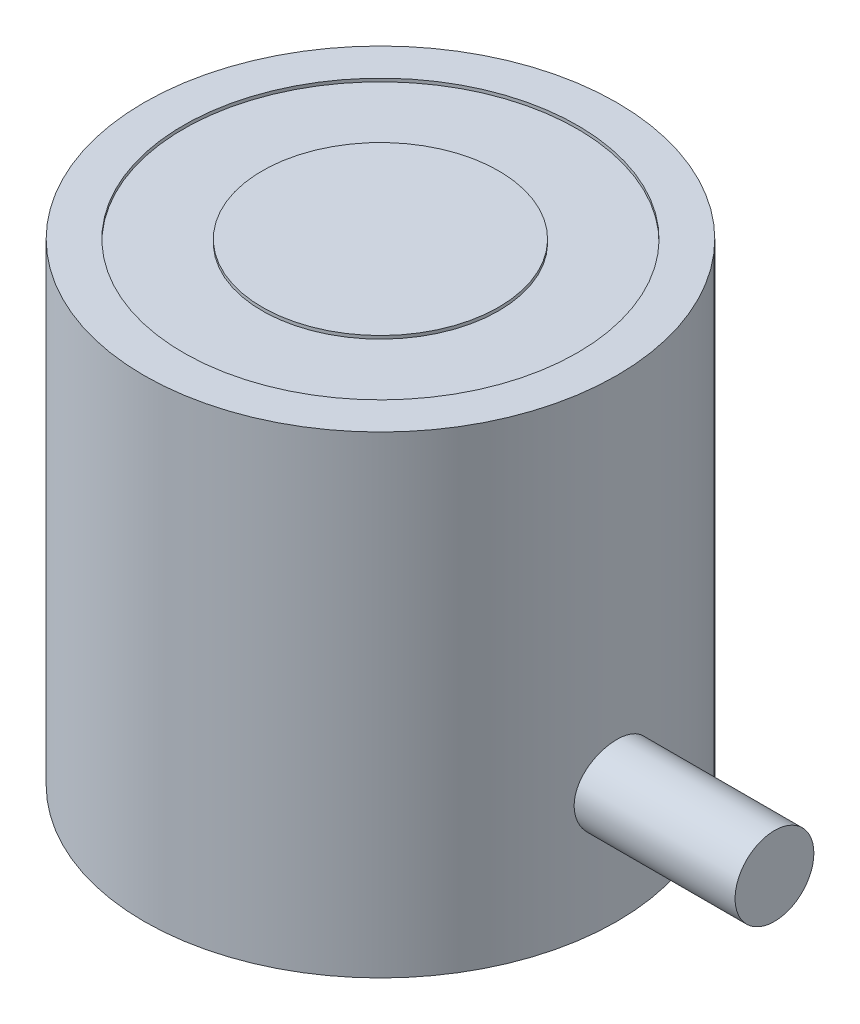
SolidWorks part; units mm, degrees
ref_plane "Front Plane" through (0, 0, 0) normal (0, 0, 1) x (1, 0, 0)
ref_plane "Top Plane" through (0, 0, 0) normal (0, 1, 0) x (1, 0, 0)
ref_plane "Right Plane" through (0, 0, 0) normal (1, 0, 0) x (0, 0, -1)
sketch "Sketch1" plane through (0, 0, 0) normal (0, 1, 0) x (1, 0, 0)
  circle A0 centre (0, 0) radius 19.05
  dimension "A" = 38.1
extrude "Boss-Extrude1" add sketch "Sketch1" along normal blind 38.1
sketch "Sketch2" plane through (0, 0, 0) normal (0, 0, 1) x (1, 0, 0)
  line L0 (-15.875, 38.1) -> (-15.875, 37.846)
  line L1 (-15.875, 37.846) -> (-9.525, 37.846)
  line L2 (-9.525, 37.846) -> (-9.525, 38.1)
  line L3 (19.05, 38.1) -> (-19.05, 38.1) construction
  line L4 (-9.525, 38.1) -> (-15.875, 38.1)
  line L5 (0, 0) -> (0, 38.1) construction
  line L6 (-19.05, 38.1) -> (-19.05, 0) construction
  dimension "D1" = 3.175
  dimension "D2" = 6.35
  dimension "D3" = 0.254
revolve "Cut-Revolve1" cut sketch "Sketch2" angle 360 about L5
sketch "Sketch3" plane through (0, 0, 0) normal (0, -1, 0) x (1, 0, 0)
  circle A0 centre (0, 0) radius 3.175
  point P3 (-3.175, 0)
  point P4 (3.175, 0)
  point P5 (0, 0)
  dimension "Hole Dia." = 6.35
extrude "Cut-Extrude1" cut sketch "Sketch3" against normal blind 12.7
sketch "Sketch4" plane through (0, 0, 0) normal (0, -1, 0) x (1, 0, 0)
  circle A1 centre (0, 0) radius 3.175
  circle A2 centre (0, 0) radius 3.175
  point P0 (-3.175, 0)
  dimension "D1" = 0
curve "Helix/Spiral1" pitch 1.27 height 13.97 turns 11 parameters "Pitch"=1.27
sketch "Sketch5" plane through (0, 0, 0) normal (0, 0, 1) x (1, 0, 0)
  line L0 (-3.3125, 0.0794) -> (-3.3125, -1.1906) construction
  line L1 (-3.3125, -1.1906) -> (-2.2126, -0.5556) construction
  line L2 (-2.2126, -0.5556) -> (-3.3125, 0.0794) construction
  line L3 (-3.175, 0) -> (-3.175, -1.1112) construction
  line L4 (-2.3501, -0.4762) -> (-2.3501, -0.635) construction
  line L5 (-2.2126, -0.5556) -> (-2.3501, -0.5556) construction
  line L6 (-2.3501, -0.5556) -> (-2.4876, -0.5556) construction
  line L7 (-3.175, -0.5556) -> (-3.3125, -0.5556) construction
  line L8 (-3.2437, -1.1509) -> (-3.2437, 0.0397)
  line L9 (-3.2437, 0.0397) -> (-2.4876, -0.3969)
  line L10 (-2.4876, -0.3969) -> (-2.4876, -0.7144)
  line L11 (-2.4876, -0.7144) -> (-3.2437, -1.1509)
  point P16 (-3.2437, -0.5556)
  dimension "D1" = 1.27
  dimension "D2" = 0.1588
sketch "Sketch6" plane through (0, 0, 0) normal (0, -1, 0) x (1, 0, 0)
  circle A0 centre (0, 0) radius 3.3125
sweep "Sweep1" add profiles "Sketch5" path "Helix/Spiral1"
extrude "Cut-Extrude2" cut sketch "Sketch6" against normal through all draft 45 and the other way through all
sketch "Sketch7" plane through (0, 0, 0) normal (1, 0, 0) x (0, 0, -1)
  line L0 (0, 9.525) -> (0, 0) construction
  circle A0 centre (0, 9.525) radius 3.175
  dimension "Wire Dia." = 6.35
  dimension "G" = 6.35
sketch "Sketch8" plane through (0, 0, 0) normal (0, 0, 1) x (1, 0, 0)
  line L0 (0, 9.525) -> (31.75, 9.525) construction
  line L1 (19.05, 0) -> (19.05, 38.1) construction
  dimension "D1" = 12.7
extrude "Boss-Extrude2" add sketch "Sketch7" against normal up to surface (12.9664 mm away) from vertex at 31.75 starting at point (31.75, 9.525, 0)
sketch "Sketch9" plane through (0, 0, 0) normal (0, 0, 1) x (1, 0, 0)
  line L0 (-3.175, 0) -> (-3.175, 12.7) construction
  line L1 (-3.175, 12.7) -> (3.175, 12.7) construction
  line L2 (3.175, 12.7) -> (3.175, 0) construction
  line L3 (-3.175, 12.7) -> (0.952, 12.7) construction
equation "\"D3@Helix/Spiral1\" = \"Pitch@Helix/Spiral1\" + \"Hole Depth@Cut-Extrude1\""
equation "\"D1@Sketch5\" = \"Pitch@Helix/Spiral1\""
equation "\"D2@Sketch5\" = \"D1@Sketch5\" / 8"
